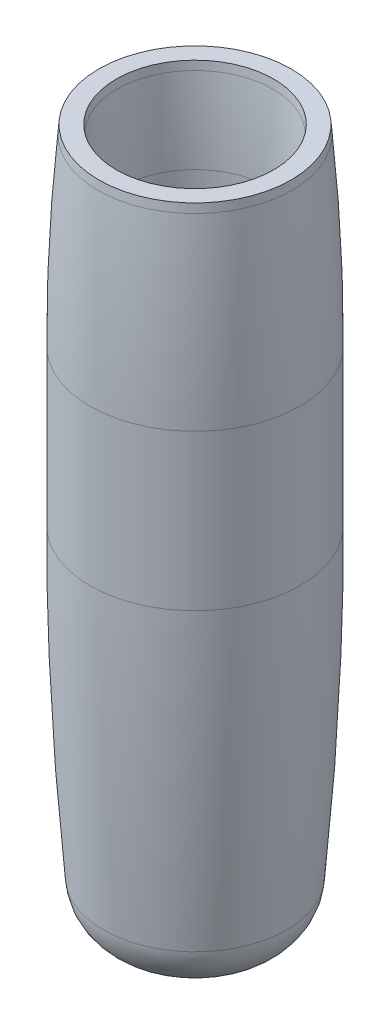
SolidWorks part; units mm, degrees
material "Nylon 101"
ref_plane "Front Plane" through (0, 0, 0) normal (0, 0, 1) x (1, 0, 0)
ref_plane "Top Plane" through (0, 0, 0) normal (0, 1, 0) x (1, 0, 0)
ref_plane "Right Plane" through (0, 0, 0) normal (1, 0, 0) x (0, 0, -1)
sketch "Sketch1" plane through (0, 0, 0) normal (0, 1, 0) x (1, 0, 0)
  circle A0 centre (0, 0) radius 6
  dimension "D1" = 12
extrude "Boss-Extrude1" add sketch "Sketch1" along normal blind 5
sketch "Sketch2" plane through (0, 5, 0) normal (0, 1, 0) x (1, 0, 0)
  circle A0 centre (0, 0) radius 4.25
  circle A1 centre (0, 0) radius 6
  circle A2 centre (0, 0) radius 6
  dimension "D2" = 8.5
  dimension "D1" = 0
extrude "Boss-Extrude2" add sketch "Sketch2" along normal blind 35
chamfer "Chamfer1" distance 1 angle 85 1 edges at (0, 0, 6) first distance on face at (0, 0, 6)
fillet "Fillet1" radius 200 1 edges at (0, 11.4301, 6)
chamfer "Chamfer2" distance 0.25 angle 85 1 edges at (0, 40, 4.25) first distance on face at (0, 40, 6)
fillet "Fillet2" radius 54.6 1 edges at (0, 37.1425, 4.25)
chamfer "Chamfer3" distance 0.5 angle 85 1 edges at (0, 40, 6) first distance on face at (0, 40, 4.5)
fillet "Fillet3" radius 120 1 edges at (0, 34.285, 6)
fillet "Fillet4" radius 3 1 edges at (0, 0, 5)
